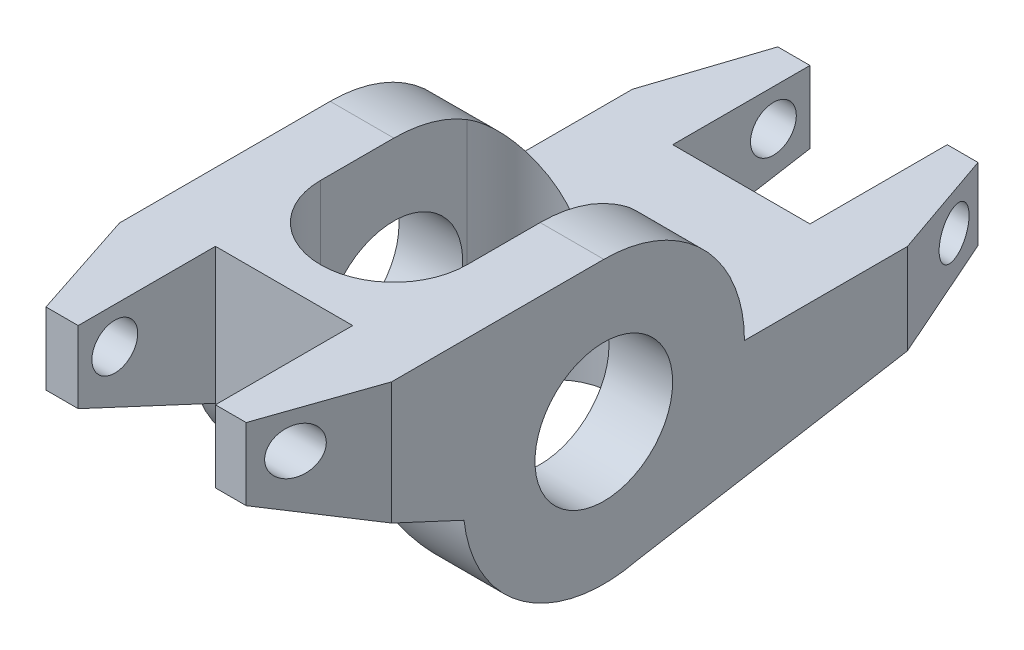
SolidWorks part; units mm, degrees
ref_plane "Front Plane" through (0, 0, 0) normal (0, 0, 1) x (1, 0, 0)
ref_plane "Top Plane" through (0, 0, 0) normal (0, 1, 0) x (1, 0, 0)
ref_plane "Right Plane" through (0, 0, 0) normal (1, 0, 0) x (0, 0, -1)
sketch "Sketch1" plane through (0, 0, 0) normal (1, 0, 0) x (0, 0, -1)
  line L0 (-15.4868, 0) -> (41.4754, 0) construction
  line L1 (0, 7.8966) -> (0, -9.93) construction
  line L2 (9.765, 0) -> (28.58, 0)
  line L3 (28.58, 0) -> (28.58, -5)
  line L4 (28.58, -5) -> (2.2735, -9.4967)
  line L5 (0, 9.765) -> (-22.23, 9.765)
  line L6 (-22.23, 9.765) -> (-22.23, 4.765)
  line L7 (-22.23, 4.765) -> (-9.7062, -1.07)
  circle A0 centre (0, 0) radius 4.78
  arc A1 (9.765, 0) -> (0, 9.765) centre (0, 0) ccw
  arc A2 (-9.7062, -1.07) -> (2.2735, -9.4967) centre (0, 0) ccw
  dimension "D1" = 9.56
  dimension "D2" = 19.53
  dimension "D3" = 28.58
  dimension "D4" = 9.7
  dimension "D5" = 5
  dimension "D6" = 5
  dimension "D7" = 22.23
  dimension "D8" = 1.07
extrude "Boss-Extrude1" add sketch "Sketch1" along normal mid plane 19
sketch "Sketch2" plane through (0, 0, 0) normal (0, 1, 0) x (1, 0, 0)
  line L0 (-23.0907, 0) -> (21.6233, 0) construction
  line L1 (0, -29.5602) -> (0, 45.6023) construction
  line L2 (9.5, 28.58) -> (-9.5, 28.58) construction
  line L3 (-4.765, 19.05) -> (4.765, 19.05)
  line L4 (-4.765, 19.05) -> (-4.765, 28.58)
  line L5 (-4.765, 28.58) -> (4.765, 28.58)
  line L6 (4.765, 19.05) -> (4.765, 28.58)
  line L7 (0, 5.08) -> (0, -5.08) construction
  line L8 (5.08, 5.08) -> (5.08, -5.08)
  line L9 (-5.08, 5.08) -> (-5.08, -5.08)
  line L10 (9.5, -22.23) -> (-9.5, -22.23) construction
  line L11 (4.765, -22.23) -> (-4.765, -22.23)
  line L12 (4.765, -22.23) -> (4.765, -12.7)
  line L13 (4.765, -12.7) -> (-4.765, -12.7)
  line L14 (-4.765, -22.23) -> (-4.765, -12.7)
  arc A0 (5.08, 5.08) -> (-5.08, 5.08) centre (0, 5.08) ccw
  arc A1 (-5.08, -5.08) -> (5.08, -5.08) centre (0, -5.08) ccw
  point P13 (0, 0)
  dimension "D1" = 9.53
  dimension "D2" = 9.53
  dimension "D3" = 10.16
  dimension "D4" = 10.16
extrude "Cut-Extrude1" cut sketch "Sketch2" against normal through all both and the other way through all
sketch "Sketch3" plane through (0, 0, 0) normal (1, 0, 0) x (0, 0, -1)
  line L0 (-22.23, 9.765) -> (-22.23, 4.765) construction
  line L1 (28.58, -5) -> (28.58, 0) construction
  line L2 (28.58, 0) -> (9.765, 0) construction
  line L3 (0, 9.765) -> (-22.23, 9.765) construction
  circle A0 centre (-19.69, 7.225) radius 1.59
  circle A1 centre (26.04, -2.54) radius 1.59
  dimension "D5" = 3.18
  dimension "D1" = 2.54
  dimension "D2" = 2.54
  dimension "D3" = 2.54
  dimension "D4" = 2.54
extrude "Cut-Extrude2" cut sketch "Sketch3" against normal through all both and the other way through all
chamfer "Chamfer1" distance 2.6 distance2 7.5 2 edges at (9.5, -2.5, -28.58) (9.5, 7.265, 22.23) first distance on face at (7.1325, -2.5, -28.58) first distance on face at (7.1325, 7.265, 22.23)
chamfer "Chamfer2" distance 7.6 distance2 2.5 2 edges at (-9.5, 7.265, 22.23) (-9.5, -2.5, -28.58) first distance on face at (-9.5, 7.225, 18.1)
